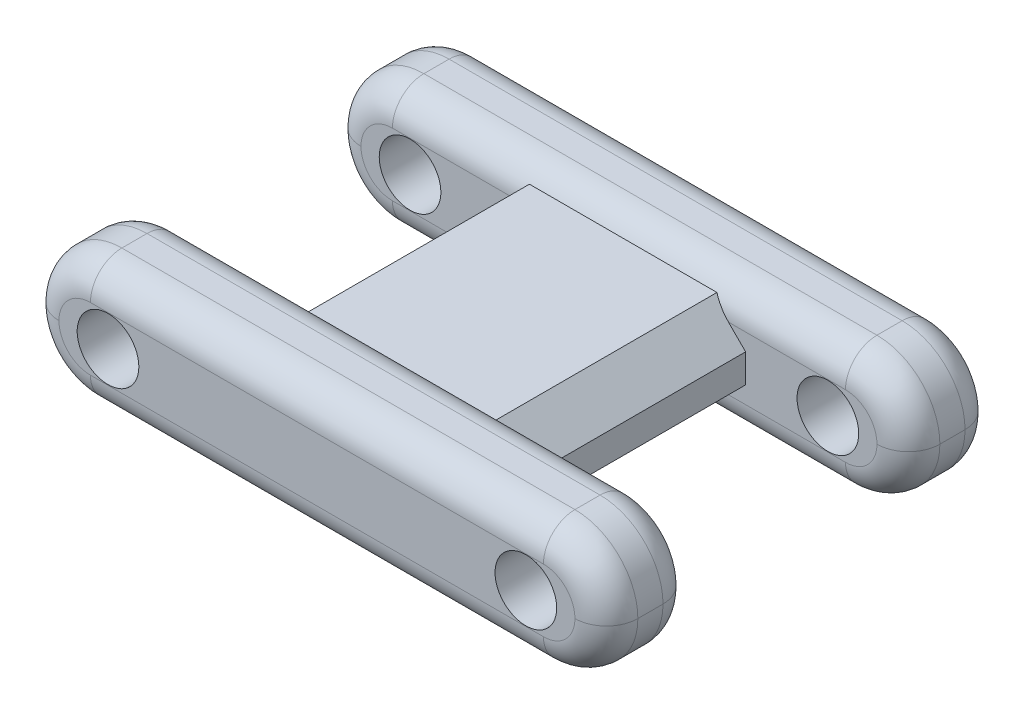
SolidWorks part; units mm, degrees
ref_plane "Front Plane" through (0, 0, 0) normal (0, 0, 1) x (1, 0, 0)
ref_plane "Top Plane" through (0, 0, 0) normal (0, 1, 0) x (1, 0, 0)
ref_plane "Right Plane" through (0, 0, 0) normal (1, 0, 0) x (0, 0, -1)
sketch "Sketch1" plane through (0, 0, 0) normal (0, 1, 0) x (1, 0, 0)
  line L0 (0, 0) -> (8195.2033, 0) construction
  line L1 (0, 0) -> (0, 8195.2033) construction
  line L2 (0, 10.795) -> (-15.24, 10.795)
  line L3 (0, -10.795) -> (-15.24, -10.795)
  line L4 (-15.24, 10.795) -> (-15.24, 19.685)
  line L5 (-15.24, -10.795) -> (-15.24, -19.685)
  line L6 (-15.24, 19.685) -> (6.35, 19.685)
  line L7 (-15.24, -19.685) -> (6.35, -19.685)
  line L8 (6.35, 19.685) -> (6.35, 6.35)
  line L9 (6.35, -19.685) -> (6.35, -6.35)
  line L10 (6.35, 6.35) -> (21.59, 6.35)
  line L11 (6.35, -6.35) -> (21.59, -6.35)
  line L12 (21.59, 6.35) -> (21.59, 19.685)
  line L13 (21.59, -6.35) -> (21.59, -19.685)
  line L14 (21.59, 19.685) -> (43.18, 19.685)
  line L15 (21.59, -19.685) -> (43.18, -19.685)
  line L16 (43.18, 19.685) -> (43.18, 10.795)
  line L17 (43.18, -19.685) -> (43.18, -10.795)
  line L18 (43.18, 10.795) -> (27.94, 10.795)
  line L19 (43.18, -10.795) -> (27.94, -10.795)
  line L20 (0, 10.795) -> (0, -10.795)
  line L21 (27.94, 10.795) -> (27.94, -10.795)
  point P6 (0, 0)
  dimension "D3" = 58.42
  dimension "D4" = 21.59
  dimension "D5" = 12.7
  dimension "D6" = 15.24
  dimension "D7" = 6.35
  dimension "D8" = 8.89
extrude "Boss-Extrude1" add sketch "Sketch1" along normal blind 12.7
sketch "Sketch2" plane through (0, 0, 19.685) normal (0, 0, 1) x (1, 0, 0)
  line L0 (-15.24, 6.35) -> (-7.1132, 6.35) construction
  line L1 (13.97, 0) -> (13.97, 50000) construction
  line L2 (-7.1132, 6.35) -> (13.97, 6.35) construction
  line L3 (13.97, 6.35) -> (35.0532, 6.35) construction
  line L4 (-15.24, 0) -> (6.35, 0)
  line L5 (6.35, 0) -> (6.35, 12.7)
  line L6 (6.35, 12.7) -> (-15.24, 12.7)
  line L7 (-15.24, 12.7) -> (-15.24, 0)
  line L8 (-15.24, 0) -> (6.35, 0)
  line L9 (6.35, 0) -> (6.35, 12.7)
  line L10 (6.35, 12.7) -> (-15.24, 12.7)
  line L11 (-15.24, 12.7) -> (-15.24, 0)
  line L12 (6.35, 0) -> (21.59, 0)
  line L13 (21.59, 0) -> (21.59, 12.7)
  line L14 (21.59, 12.7) -> (6.35, 12.7)
  line L15 (6.35, 12.7) -> (6.35, 0)
  line L16 (6.35, 0) -> (21.59, 0)
  line L17 (21.59, 0) -> (21.59, 12.7)
  line L18 (21.59, 12.7) -> (6.35, 12.7)
  line L19 (6.35, 12.7) -> (6.35, 0)
  line L20 (21.59, 0) -> (43.18, 0)
  line L21 (43.18, 0) -> (43.18, 12.7)
  line L22 (43.18, 12.7) -> (21.59, 12.7)
  line L23 (21.59, 12.7) -> (21.59, 0)
  line L24 (21.59, 0) -> (43.18, 0)
  line L25 (43.18, 0) -> (43.18, 12.7)
  line L26 (43.18, 12.7) -> (21.59, 12.7)
  line L27 (21.59, 12.7) -> (21.59, 0)
  line L28 (35.0532, 6.35) -> (43.18, 6.35) construction
  circle A0 centre (-7.1132, 6.35) radius 3.1115
  circle A1 centre (35.0532, 6.35) radius 3.1115
  point P14 (13.97, 0)
  dimension "D4" = 6.223
  dimension "D5" = 42.1663
  dimension "D1" = 0
  dimension "D2" = 0
  dimension "D3" = 0
extrude "Cut-Extrude1" cut sketch "Sketch2" against normal through all contours A1 | A0 region at (-7.1132, 6.35, 19.685) region at (35.0532, 6.35, 19.685)
fillet "Fillet5" radius 6.35 8 edges at (43.18, 0, 15.24) (43.18, 12.7, 15.24) (43.18, 0, -15.24) (43.18, 12.7, -15.24) (-15.24, 12.7, 15.24) (-15.24, 0, 15.24) (-15.24, 0, -15.24) (-15.24, 12.7, -15.24)
fillet "Fillet6" radius 3.175 32 edges at (29.21, 0, 19.685) (41.3201, 1.8599, 19.685) (41.3201, 10.8401, 19.685) (29.21, 0, -19.685) (41.3201, 1.8599, -19.685) (41.3201, 10.8401, -19.685) (-1.27, 0, -19.685) (-13.3801, 1.8599, -19.685) (-13.3801, 10.8401, -19.685) (-1.27, 12.7, 19.685) (-1.27, 0, 19.685) (-13.3801, 1.8599, 19.685) (-4.445, 12.7, -10.795) (-4.445, 0, -10.795) (-13.3801, 1.8599, -10.795) (-4.445, 0, 10.795) (-13.3801, 1.8599, 10.795) (-4.445, 12.7, 10.795) (32.385, 0, -10.795) (41.3201, 1.8599, -10.795) (32.385, 12.7, -10.795) (32.385, 12.7, 10.795) (32.385, 0, 10.795) (41.3201, 1.8599, 10.795) (29.21, 12.7, 19.685) (29.21, 12.7, -19.685) (-1.27, 12.7, -19.685) (-13.3801, 10.8401, 19.685) (-13.3801, 10.8401, -10.795) (-13.3801, 10.8401, 10.795) (41.3201, 10.8401, -10.795) (41.3201, 10.8401, 10.795)
chamfer "Chamfer1" distance 6.096 angle 45 4 edges at (0, 12.7, 0) (27.94, 0, 0) (27.94, 12.7, 0) (0, 0, 0)
ref_plane "Plane1" through (27.94, 0, 0) normal (1, 0, 0) x (0, 0, -1)
sketch "Sketch4" plane through (27.94, 0, 0) normal (1, 0, 0) x (0, 0, -1)
  line L4 (-10.795, 6.604) -> (-10.795, 6.096)
  line L5 (-10.795, 6.096) -> (10.795, 6.096)
  line L6 (10.795, 6.096) -> (10.795, 6.604)
  line L7 (10.795, 6.604) -> (-10.795, 6.604)
  line L8 (-10.795, 6.604) -> (-10.795, 6.096)
  line L9 (-10.795, 6.096) -> (10.795, 6.096)
  line L10 (10.795, 6.096) -> (10.795, 6.604)
  line L11 (10.795, 6.604) -> (-10.795, 6.604)
  line L12 (13.97, 0) -> (-13.97, 0) construction
  line L13 (-13.97, 12.7) -> (13.97, 12.7) construction
  line L18 (13.97, 0) -> (-13.97, 0)
  line L20 (0, 12.7) -> (0, 0) construction
  line L21 (-6.35, 12.7) -> (-6.35, 0)
  line L22 (6.35, 12.7) -> (6.35, 0)
  line L23 (-6.35, 11.1125) -> (6.35, 11.1125)
  line L24 (0, 6.35) -> (50000, 6.35) construction
  line L25 (-13.97, 0) -> (13.97, 0)
  line L26 (-6.35, 1.5875) -> (6.35, 1.5875)
  line L27 (-6.35, 12.7) -> (6.35, 12.7)
  point P20 (0, 6.35)
  dimension "D4" = 1.5875
  dimension "D1" = 0
  dimension "D2" = 6.35
  dimension "D3" = 6.35
extrude "Cut-Extrude2" cut sketch "Sketch4" against normal up to surface (21.844 mm away) contours L21 L23 L22 | L26 L21 L18 L22 region at (27.94, 11.9062, 0) region at (27.94, 0.7938, 0) up to face at (3.2249, 9.8289, 0)
sketch "Sketch5" plane through (0, 0, 6.35) normal (0, 0, -1) x (-1, 0, 0)
  line L4 (-6.35, 11.1125) -> (-4.5085, 11.1125)
  line L5 (-4.5085, 11.1125) -> (-6.096, 12.7)
  line L6 (-6.096, 12.7) -> (-6.35, 12.7)
  line L7 (-6.35, 12.7) -> (-6.35, 11.1125)
  line L8 (-6.35, 11.1125) -> (-4.5085, 11.1125)
  line L9 (-4.5085, 11.1125) -> (-6.096, 12.7)
  line L13 (-6.35, 12.7) -> (-6.35, 11.1125)
  line L14 (-6.096, 12.7) -> (-6.35, 12.7)
  dimension "D1" = 0
extrude "Cut-Extrude3" cut sketch "Sketch5" against normal up to surface and the other way up to surface up to face at (-2.0264, 11.4413, 12.0537) other way up to face at (-2.0264, 11.4413, -12.0537)
sketch "Sketch6" plane through (0, 0, 6.35) normal (0, 0, -1) x (-1, 0, 0)
  line L4 (-21.59, 12.7) -> (-21.844, 12.7)
  line L12 (-21.844, 12.7) -> (-23.4315, 11.1125)
  line L14 (-21.844, 12.7) -> (-23.4315, 11.1125)
  line L16 (-23.4315, 11.1125) -> (-21.59, 11.1125)
  line L17 (-23.4315, 11.1125) -> (-21.59, 11.1125)
  line L18 (-21.59, 11.1125) -> (-21.59, 12.7)
  line L19 (-21.59, 11.1125) -> (-21.59, 12.7)
  line L20 (-21.59, 12.7) -> (-21.844, 12.7)
  dimension "D1" = 0
extrude "Cut-Extrude4" cut sketch "Sketch6" against normal up to surface and the other way up to surface up to face at (29.9664, 11.4413, 12.0537) other way up to face at (29.9664, 11.4413, -12.0537)
sketch "Sketch7" plane through (0, 0, -6.35) normal (0, 0, 1) x (1, 0, 0)
  line L4 (21.59, 1.5875) -> (21.59, 0)
  line L5 (21.59, 0) -> (21.844, 0)
  line L6 (21.844, 0) -> (23.4315, 1.5875)
  line L7 (23.4315, 1.5875) -> (21.59, 1.5875)
  line L10 (21.844, 0) -> (23.4315, 1.5875)
  line L11 (23.4315, 1.5875) -> (21.59, 1.5875)
  line L13 (21.59, 1.5875) -> (21.59, 0)
  line L14 (21.59, 0) -> (21.844, 0)
  dimension "D1" = 0
extrude "Cut-Extrude5" cut sketch "Sketch7" against normal up to surface and the other way up to surface up to face at (29.9664, 1.2587, -12.0537) other way up to face at (29.9664, 1.2587, 12.0537)
sketch "Sketch8" plane through (0, 0, -6.35) normal (0, 0, 1) x (1, 0, 0)
  line L4 (6.35, 0) -> (6.35, 1.5875)
  line L5 (6.35, 1.5875) -> (4.5085, 1.5875)
  line L6 (4.5085, 1.5875) -> (6.096, 0)
  line L7 (6.096, 0) -> (6.35, 0)
  line L8 (6.35, 0) -> (6.35, 1.5875)
  line L9 (6.35, 1.5875) -> (4.5085, 1.5875)
  line L10 (4.5085, 1.5875) -> (6.096, 0)
  line L12 (6.096, 0) -> (6.35, 0)
  dimension "D1" = 0
extrude "Cut-Extrude6" cut sketch "Sketch8" against normal up to surface and the other way up to surface up to face at (-2.0264, 1.2587, -12.0537) other way up to face at (-2.0264, 1.2587, 12.0537)
sketch "Sketch9" plane through (0, 11.1125, 0) normal (0, 1, 0) x (1, 0, 0)
  line L0 (27.94, 10.795) -> (27.94, -10.795) construction
  line L1 (27.94, 10.795) -> (27.94, -10.795)
  line L2 (26.7494, 10.795) -> (26.7494, -10.795)
  line L3 (27.94, 10.795) -> (26.7494, 10.795)
  line L4 (27.94, -10.795) -> (26.7494, -10.795)
  line L5 (13.97, -6.35) -> (13.97, 6.35) construction
  line L6 (0, -10.795) -> (1.1906, -10.795)
  line L7 (0, 10.795) -> (0, -10.795)
  line L8 (0, 10.795) -> (1.1906, 10.795)
  line L9 (1.1906, 10.795) -> (1.1906, -10.795)
  line L15 (23.4315, -11.2204) -> (23.4315, 11.2204)
  line L19 (21.59, -6.35) -> (21.59, -11.2204)
  line L21 (4.5085, 11.2204) -> (4.5085, -11.2204)
  line L22 (6.35, 6.35) -> (6.35, 11.2204)
  line L27 (23.4315, -11.2204) -> (23.4315, 11.2204)
  line L33 (4.5085, 11.2204) -> (4.5085, -11.2204)
  line L36 (21.59, -6.35) -> (21.59, -11.2204)
  line L38 (6.35, -6.35) -> (21.59, -6.35)
  line L39 (6.35, -6.35) -> (21.59, -6.35)
  line L40 (6.35, 6.35) -> (6.35, 11.2204)
  line L48 (21.59, 6.35) -> (6.35, 6.35)
  line L49 (21.59, 6.35) -> (6.35, 6.35)
  line L50 (6.35, 11.2204) -> (4.5085, 11.2204)
  line L52 (6.35, 11.2204) -> (4.5085, 11.2204)
  line L54 (4.5085, -11.2204) -> (6.35, -11.2204)
  line L55 (4.5085, -11.2204) -> (6.35, -11.2204)
  line L56 (6.35, -11.2204) -> (6.35, -6.35)
  line L57 (6.35, -11.2204) -> (6.35, -6.35)
  line L60 (21.59, -11.2204) -> (23.4315, -11.2204)
  line L61 (21.59, -11.2204) -> (23.4315, -11.2204)
  line L62 (23.4315, 11.2204) -> (21.59, 11.2204)
  line L63 (23.4315, 11.2204) -> (21.59, 11.2204)
  line L64 (21.59, 11.2204) -> (21.59, 6.35)
  line L65 (21.59, 11.2204) -> (21.59, 6.35)
  point P5 (13.97, 6.35)
  dimension "D1" = 0
  dimension "D2" = 1.1906
extrude "Cut-Extrude7" cut sketch "Sketch9" against normal through all contours L4 L1 L3 L2 | L9 L8 L7 L6 region at (27.3447, 11.1125, 0) region at (0.5953, 11.1125, 0)
sketch "Sketch10" plane through (6.35, 0, 0) normal (1, 0, 0) x (0, 0, -1)
  line L4 (6.35, 11.1125) -> (6.35, 1.5875)
  line L6 (19.685, 3.175) -> (19.685, 9.525)
  line L8 (6.35, 11.1125) -> (6.35, 1.5875)
  line L10 (19.685, 3.175) -> (19.685, 9.525)
  line L13 (6.35, 1.5875) -> (11.2204, 1.5875)
  line L14 (13.97, 0) -> (16.51, 0)
  line L15 (13.97, 0) -> (16.51, 0)
  line L16 (16.51, 12.7) -> (13.97, 12.7)
  line L17 (16.51, 12.7) -> (13.97, 12.7)
  line L18 (6.35, 1.5875) -> (11.2204, 1.5875)
  line L22 (11.2204, 11.1125) -> (6.35, 11.1125)
  line L23 (11.2204, 11.1125) -> (6.35, 11.1125)
  arc A2 (16.51, 0) -> (19.685, 3.175) centre (16.51, 3.175) ccw
  arc A3 (16.51, 0) -> (19.685, 3.175) centre (16.51, 3.175) ccw
  arc A6 (19.685, 9.525) -> (16.51, 12.7) centre (16.51, 9.525) ccw
  arc A7 (19.685, 9.525) -> (16.51, 12.7) centre (16.51, 9.525) ccw
  arc A13 (13.97, 12.7) -> (11.2204, 11.1125) centre (13.97, 9.525) ccw
  arc A14 (13.97, 12.7) -> (11.2204, 11.1125) centre (13.97, 9.525) ccw
  arc A16 (11.2204, 1.5875) -> (13.97, 0) centre (13.97, 3.175) ccw
  arc A17 (11.2204, 1.5875) -> (13.97, 0) centre (13.97, 3.175) ccw
  dimension "D1" = 0
extrude "Boss-Extrude2" add sketch "Sketch10" along normal up to surface (15.24 mm away) up to face at (21.59, 6.35, -13.636)
sketch "Sketch12" plane through (6.35, 0, 0) normal (1, 0, 0) x (0, 0, -1)
  line L5 (-6.35, 1.5875) -> (-6.35, 11.1125)
  line L7 (-19.685, 9.525) -> (-19.685, 3.175)
  line L9 (-6.35, 1.5875) -> (-6.35, 11.1125)
  line L11 (-19.685, 9.525) -> (-19.685, 3.175)
  line L13 (-11.2204, 1.5875) -> (-6.35, 1.5875)
  line L14 (-13.97, 12.7) -> (-16.51, 12.7)
  line L15 (-13.97, 12.7) -> (-16.51, 12.7)
  line L16 (-16.51, 0) -> (-13.97, 0)
  line L17 (-16.51, 0) -> (-13.97, 0)
  line L18 (-11.2204, 1.5875) -> (-6.35, 1.5875)
  line L22 (-6.35, 11.1125) -> (-11.2204, 11.1125)
  line L23 (-6.35, 11.1125) -> (-11.2204, 11.1125)
  arc A2 (-19.685, 3.175) -> (-16.51, 0) centre (-16.51, 3.175) ccw
  arc A3 (-19.685, 3.175) -> (-16.51, 0) centre (-16.51, 3.175) ccw
  arc A6 (-16.51, 12.7) -> (-19.685, 9.525) centre (-16.51, 9.525) ccw
  arc A7 (-16.51, 12.7) -> (-19.685, 9.525) centre (-16.51, 9.525) ccw
  arc A13 (-13.97, 0) -> (-11.2204, 1.5875) centre (-13.97, 3.175) ccw
  arc A14 (-13.97, 0) -> (-11.2204, 1.5875) centre (-13.97, 3.175) ccw
  arc A16 (-11.2204, 11.1125) -> (-13.97, 12.7) centre (-13.97, 9.525) ccw
  arc A17 (-11.2204, 11.1125) -> (-13.97, 12.7) centre (-13.97, 9.525) ccw
  dimension "D1" = 0
extrude "Boss-Extrude3" add sketch "Sketch12" along normal up to surface (15.24 mm away) up to face at (21.59, 6.35, 13.636)
sketch "Sketch13" plane through (0, 11.1125, 0) normal (0, 1, 0) x (1, 0, 0)
  line L4 (23.4315, -11.2204) -> (23.4315, 11.2204)
  line L5 (23.4315, 11.2204) -> (4.5085, 11.2204)
  line L6 (4.5085, 11.2204) -> (4.5085, -11.2204)
  line L7 (4.5085, -11.2204) -> (23.4315, -11.2204)
  line L8 (23.4315, -11.2204) -> (23.4315, 11.2204)
  line L9 (23.4315, 11.2204) -> (4.5085, 11.2204)
  line L10 (4.5085, 11.2204) -> (4.5085, -11.2204)
  line L11 (4.5085, -11.2204) -> (23.4315, -11.2204)
  line L12 (26.7494, -10.795) -> (26.7494, 10.795)
  line L13 (26.7494, 10.795) -> (25.019, 10.795)
  line L14 (23.4315, 11.2204) -> (23.4315, -11.2204)
  line L15 (25.019, -10.795) -> (26.7494, -10.795)
  line L16 (26.7494, -10.795) -> (26.7494, 10.795)
  line L17 (26.7494, 10.795) -> (25.019, 10.795)
  line L18 (23.4315, 11.2204) -> (23.4315, -11.2204)
  line L19 (25.019, -10.795) -> (26.7494, -10.795)
  arc A2 (23.4315, 11.2204) -> (25.019, 10.795) centre (25.019, 13.97) ccw
  arc A3 (25.019, -10.795) -> (23.4315, -11.2204) centre (25.019, -13.97) ccw
  arc A4 (23.4315, 11.2204) -> (25.019, 10.795) centre (25.019, 13.97) ccw
  arc A5 (25.019, -10.795) -> (23.4315, -11.2204) centre (25.019, -13.97) ccw
  dimension "D1" = 0
  dimension "D2" = 0
